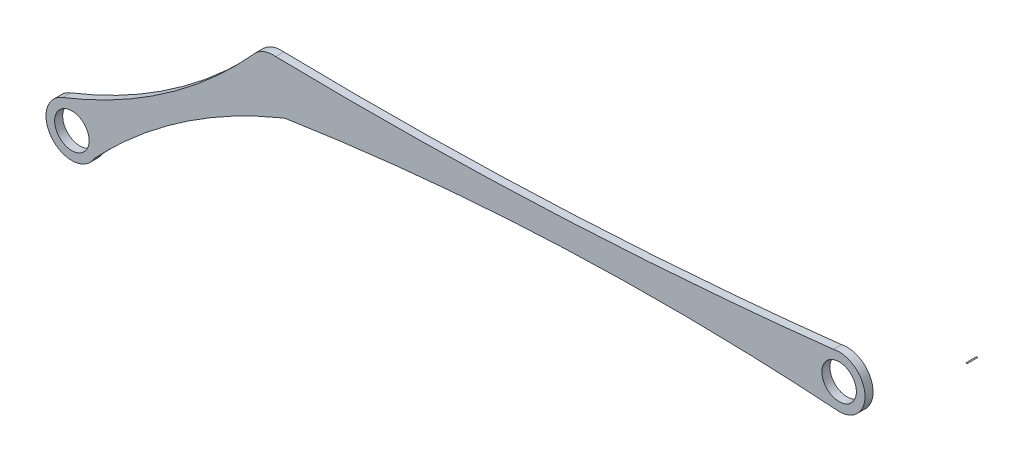
SolidWorks part; units mm, degrees
material "1060 Alloy"
ref_plane "Front Plane" through (0, 0, 0) normal (0, 0, 1) x (1, 0, 0)
ref_plane "Top Plane" through (0, 0, 0) normal (0, 1, 0) x (1, 0, 0)
ref_plane "Right Plane" through (0, 0, 0) normal (1, 0, 0) x (0, 0, -1)
sketch "Sketch1" plane through (0, 0, 0) normal (0, 0, 1) x (1, 0, 0)
  line L0 (0, 0) -> (279.4, 0) construction
  line L1 (7.0023, 16.6052) -> (278.5791, 25.3867)
  line L2 (16.974, -33.8989) -> (280.2209, -25.3867)
  line L3 (0, 0) -> (-97.2876, -81.634) construction
  line L4 (2.6264, -38.9122) -> (-82.1191, -102.0074)
  line L5 (-10.5891, 14.582) -> (-112.4562, -61.2606)
  arc A0 (7.0023, 16.6052) -> (-10.5891, 14.582) centre (0, 0) ccw
  arc A1 (280.2209, -25.3867) -> (278.5791, 25.3867) centre (279.4, 0) ccw
  arc A3 (-112.4562, -61.2606) -> (-82.1191, -102.0074) centre (-97.2876, -81.634) ccw
  arc A4 (0, 18.0212) -> (-10.5891, 14.582) centre (0, 0) ccw
  arc A5 (2.6264, -38.9122) -> (16.974, -33.8989) centre (17.7949, -59.2856) cw
  circle A6 centre (-97.2876, -81.634) radius 8.4667
  circle A7 centre (279.4, 0) radius 8.4667
  point P3 (114.3, 0)
  point P10 (-50.9335, -37.9213)
  dimension "D2" = 127
  dimension "D3" = 50.8
  dimension "D4" = 16.9333
  dimension "D8" = 25.4
  dimension "D9" = 25.4
  dimension "D1" = 279.4
  dimension "D6" = 140
  dimension "D7" = 50.8
extrude "Boss-Extrude1" add sketch "Sketch1" along normal blind 3.9688 contours L4 A5 L2 A1 L1 A0 L5 A3 A7 A6 region at (83.2082, -18.5753, 0)
sketch "Sketch2" plane through (0, 0, 3.9688) normal (0, 0, 1) x (1, 0, 0)
  line L0 (16.974, -33.8989) -> (280.2209, -25.3867) construction
  line L1 (7.0023, 16.6052) -> (278.5791, 25.3867) construction
  line L2 (-97.2876, -81.634) -> (1.5952, -12.7) construction
  line L3 (-134.3295, -73.2391) -> (-53.9694, -4.7447)
  line L4 (-93.0845, -119.382) -> (5.3912, -67.5917)
  line L5 (279.4, 0) -> (1.5952, -12.7) construction
  line L6 (280.56, -25.3735) -> (5.3912, -67.5917)
  line L7 (278.24, 25.3735) -> (46.7414, 20.6549)
  arc A0 (-101.7594, -69.7473) -> (-86.2073, -87.8401) centre (-97.2876, -81.634) ccw
  arc A1 (277.6706, -12.5817) -> (276.5811, 12.3832) centre (279.4, 0) ccw
  arc A2 (5.3912, -24.8194) -> (7.3439, -24.0245) centre (1.5952, -12.7) ccw
  arc A3 (16.974, -33.8989) -> (2.6264, -38.9122) centre (17.7949, -59.2856) ccw construction
  arc A4 (2.8221, -0.0594) -> (-8.3044, -4.7447) centre (1.5952, -12.7) ccw
  arc A5 (-134.3295, -73.2391) -> (-93.0845, -119.382) centre (-97.2876, -81.634) ccw
  arc A6 (46.7414, 20.6549) -> (-53.9694, -4.7447) centre (1.5952, -12.7) ccw
  arc A7 (280.56, -25.3735) -> (278.24, 25.3735) centre (279.4, 0) ccw
  arc A8 (46.7414, 20.6549) -> (-30.5051, 33.3466) centre (1.5952, -12.7) ccw
  spline S0 degree 2 poles (7.3439, -24.0245) (-46.6543, -45.771) (-86.2073, -87.8401) knots 0 0 0 1 1 1
  spline S1 degree 2 poles (-102.152, -69.9025) (-47.7798, -48.4603) (-8.3044, -4.7447) knots 0 0 0 1 1 1
  spline S2 degree 2 poles (0, 0) (140.154, -3.0443) (279.4, 12.7) knots 0 0 0 1 1 1
  spline S3 degree 2 poles (7.3439, -24.0245) (142.7973, -3.2601) (279.4, -12.7) knots 0 0 0 1 1 1
  point P4 (-47.8462, -47.167)
  point P20 (9.4165, -35.3073)
  point P35 (140.4976, -6.35)
  line M6 (-82.1191, -102.0074) -> (2.6264, -38.9122)
  arc M7 (2.6264, -38.9122) -> (16.974, -33.8989) centre (17.7949, -59.2856) cw
  line M8 (16.974, -33.8989) -> (280.2209, -25.3867)
  arc M9 (280.2209, -25.3867) -> (278.5791, 25.3867) centre (279.4, 0) ccw
  line M10 (278.5791, 25.3867) -> (7.0023, 16.6052)
  arc M11 (7.0023, 16.6052) -> (-10.5891, 14.582) centre (0, 0) ccw
  line M12 (-10.5891, 14.582) -> (-112.4562, -61.2606)
  arc M13 (-112.4562, -61.2606) -> (-82.1191, -102.0074) centre (-97.2876, -81.634) ccw
  dimension "D1" = 25.4
  dimension "D2" = 25.4
  dimension "D3" = 22.6073
  dimension "D4" = 19.05
  dimension "D5" = 19.05
extrude "Cut-Extrude1" cut sketch "Sketch2" against normal through all contours A7 L7 S3 A2 S0 A0 S1 A4 S2 A1 M9 M10 M11 M12 M13 M6 M7 M8 | L7 A6 L3 A5 L4 L6 M9 M8 M7 M6 M13 M12 M11 M10 region at (21.4845, -36.3339, 3.9688) region at (82.2202, -18.9198, 3.9688)
scale "Scale1" bodies to scale 102 scale about centroid uniform scaling yes scale factor 0.75
